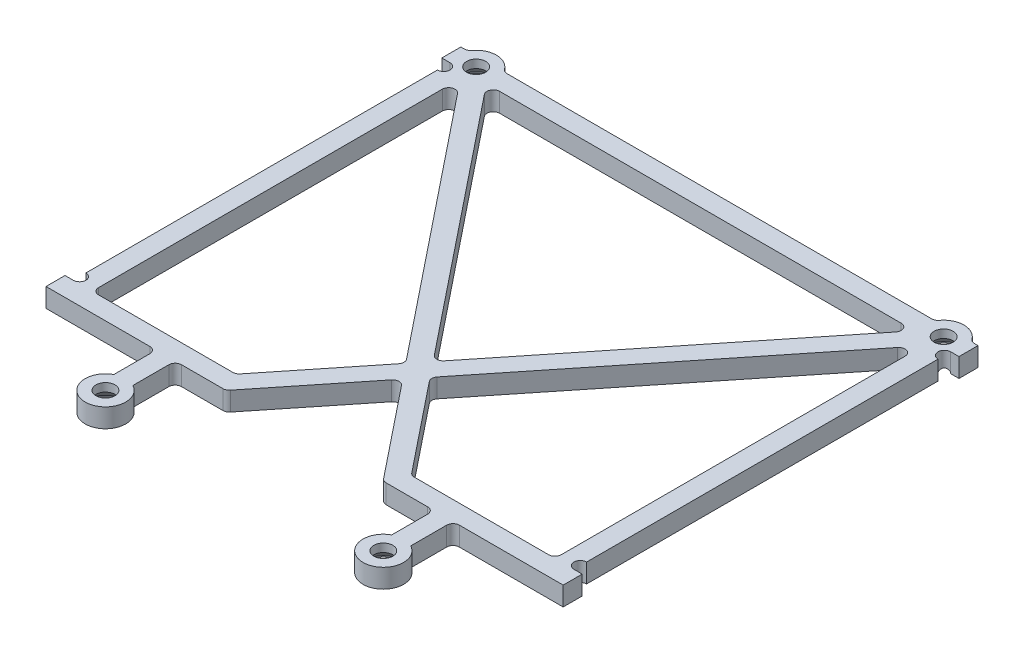
SolidWorks part; units mm, degrees
ref_plane "Front Plane" through (0, 0, 0) normal (0, 0, 1) x (1, 0, 0)
ref_plane "Top Plane" through (0, 0, 0) normal (0, 1, 0) x (1, 0, 0)
ref_plane "Right Plane" through (0, 0, 0) normal (1, 0, 0) x (0, 0, -1)
sketch "Sketch1" plane through (0, 0, 0) normal (0, 1, 0) x (1, 0, 0)
  line L0 (-36.88, 36.725) -> (36.88, 36.725) construction
  line L1 (-39.5, -24.225) -> (-39.5, 35.225)
  line L2 (21.92, -36.725) -> (-21.92, -36.725) construction
  line L3 (-36.5, -24.225) -> (-36.5, 35.225)
  line L4 (0, -40.095) -> (0, -36.725) construction
  line L5 (0, 36.725) -> (0, -36.725) construction
  line L6 (40.8, 38.225) -> (-40.8, 38.225)
  line L9 (40.8, 38.225) -> (40.8, 35.225)
  line L17 (40.8, 35.225) -> (-40.8, 35.225)
  line L18 (-40.8, 38.225) -> (-40.8, 35.225)
  line L23 (40.8, 38.225) -> (-40.8, 35.225) construction
  line L24 (40.8, 35.225) -> (-40.8, 38.225) construction
  line L60 (-21.92, -36.725) -> (36.88, 36.725) construction
  line L62 (21.92, -36.725) -> (-36.88, 36.725) construction
  line L66 (23.091, -35.7876) -> (-35.709, 37.6624)
  line L67 (20.749, -37.6624) -> (-38.051, 35.7876)
  line L68 (-20.749, -37.6624) -> (38.051, 35.7876)
  line L69 (-23.091, -35.7876) -> (35.709, 37.6624)
  line L71 (-36.5, 5.5) -> (-39.5, 5.5) construction
  line L73 (36.5, -24.225) -> (36.5, 35.225)
  line L74 (39.5, -24.225) -> (39.5, 35.225)
  line L75 (-36.5, -24.225) -> (-36.5, -27.225) construction
  line L76 (-40.8, -24.225) -> (40.8, -24.225)
  line L77 (-40.8, -24.225) -> (-40.8, -27.225)
  line L78 (-40.8, -27.225) -> (40.8, -27.225)
  line L79 (40.8, -24.225) -> (40.8, -27.225)
  line L80 (-40.8, -24.225) -> (40.8, -27.225) construction
  line L81 (-40.8, -27.225) -> (40.8, -24.225) construction
  line L82 (-21.92, -36.725) -> (-21.92, -27.225) construction
  line L84 (-23.42, -27.225) -> (-20.42, -27.225)
  line L85 (-23.42, -27.225) -> (-23.42, -33.8983)
  line L86 (-23.42, -33.8983) -> (-20.42, -33.8983)
  line L87 (-20.42, -27.225) -> (-20.42, -33.8983)
  line L88 (-23.42, -27.225) -> (-20.42, -33.8983) construction
  line L89 (-23.42, -33.8983) -> (-20.42, -27.225) construction
  line L90 (20.42, -27.225) -> (20.42, -33.8983)
  line L91 (23.42, -27.225) -> (23.42, -33.8983)
  circle A0 centre (21.92, -36.725) radius 1.5
  circle A1 centre (-21.92, -36.725) radius 1.5
  circle A2 centre (-36.88, 36.725) radius 1.5
  circle A3 centre (36.88, 36.725) radius 1.5
  circle A4 centre (-36.88, 36.725) radius 3.2
  circle A5 centre (-21.92, -36.725) radius 3.2
  circle A6 centre (21.92, -36.725) radius 3.2
  circle A7 centre (36.88, 36.725) radius 3.2
  circle A8 centre (0, -40.095) radius 16
  circle A9 centre (-39.5, 34.225) radius 1
  circle A10 centre (39.5, 34.225) radius 1
  circle A11 centre (-39.5, -23.225) radius 1
  circle A12 centre (39.5, -23.225) radius 1
  point P10 (0, 0)
  point P18 (-21.92, -30.5617)
  point P58 (0, -25.725)
  dimension "D4" = 3
  dimension "D5" = 6.4
  dimension "D6" = 32
  dimension "D9" = 3
  dimension "D17" = 2
  dimension "D1" = 74.958
  dimension "D2" = 43.84
  dimension "D3" = 73.76
  dimension "D7" = 3.37
  dimension "D8" = 81.6
  dimension "D10" = 79
  dimension "D13" = 1.5
  dimension "D14" = 1.5
  dimension "D15" = 1.5
  dimension "D16" = 1.5
  dimension "D18" = 11
extrude "Shape" add sketch "Sketch1" along normal blind 3 contours L9 | L9 | A4 L6 L18 L17 | L6 A4 | L6 A4 L17 L67 A2 | L66 A4 L6 A2 | L17 A4 L66 A2 | L67 A4 L17 L3 | L67 L3 L17 | A2 L67 L17 | A9 A4 L3 L67 L17 | A11 L76 L3 A4 A9 L1 | A4 L67 L69 L66 L17 | A4 L17 L66 | A7 L6 A4 L66 L17 L69 | L6 A7 L69 A3 | L6 A7 | L17 A7 L6 A3 L68 | A7 L17 L9 L6 | A7 A10 L17 L68 L73 | A3 L17 L68 | L69 A7 L17 A3 | L17 A7 L68 L73 | L73 L68 L17 | A7 L69 L17 | A7 L17 L69 L66 L68 | L76 A12 L74 A10 A7 L73 | L69 L67 L68 L66 | L69 L76 L68 L67 | L67 L76 L66 L68 | L77 L78 L69 L76 | A5 L69 L87 L78 L85 | A5 L87 L69 | L86 A5 L69 | L69 A5 L86 | L86 A5 L68 A1 L69 | L68 A5 L86 L69 A1 | L69 L78 L68 L76 | L67 L78 L66 L76 | L79 L76 L66 L78 | A6 L91 L78 L90 L66 | A6 L66 L90 | A6 L66 A0 L67 | L66 A6 L67 A0 region at (-27.9084, 0, 25.7017) region at (-37.9894, 0, -4.9296) region at (-37.7315, 0, -34.3772) region at (-13.114, 0, 25.725) region at (-6.4791, 0, 17.3668) region at (-21.9608, 0, 30.3398) region at (-36.8669, 0, -34.7667) region at (-35.5453, 0, -34.5717) region at (-17.9573, 0, -13.0823) region at (0, 0, 9.3436) region at (-39.0008, 0, -36.743) region at (-40.3721, 0, -36.725) region at (-22.2364, 0, 33.7343) region at (-22.4993, 0, 33.9863) region at (-35.0617, 0, -35.8515) region at (-37.5447, 0, -35.3415) region at (-33.9168, 0, -35.3014) region at (-20.7161, 0, 33.2949) region at (6.4791, 0, 17.3668) region at (17.9573, 0, -13.0823) region at (-36.88, 0, -38.9233) region at (-20.5884, 0, 35.1329) region at (-21.0809, 0, 33.7851) region at (0, 0, -36.7255) region at (-34.6096, 0, -37.2433) region at (13.114, 0, 25.725) region at (33.9168, 0, -35.3014) region at (27.9084, 0, 25.7017) region at (35.5453, 0, -34.5717) region at (35.0617, 0, -35.8515) region at (34.6096, 0, -37.2433) region at (36.88, 0, -38.9233) region at (20.6063, 0, 35.084) region at (19.7951, 0, 36.6157) region at (37.9894, 0, -4.9296) region at (36.8669, 0, -34.7667) region at (37.7315, 0, -34.3772) region at (39.0008, 0, -36.743) region at (40.3721, 0, -36.725) region at (20.7161, 0, 33.2949) region at (21.9608, 0, 30.3398) region at (37.5447, 0, -35.3415)
fillet "Mill fillets" radius 1 22 edges at (39.7067, 1.5, -38.225) (34.0533, 1.5, -38.225) (-39.7067, 1.5, -38.225) (-34.0533, 1.5, -38.225) (1.9214, 1.5, 9.3436) (-1.9214, 1.5, 9.3436) (33.7577, 1.5, -35.225) (-33.7577, 1.5, -35.225) (0, 1.5, 11.7438) (-36.5, 1.5, 24.225) (13.8346, 1.5, 24.225) (36.5, 1.5, 24.225) (-13.8346, 1.5, 24.225) (36.5, 1.5, -33.8501) (-36.5, 1.5, -33.8501) (0, 1.5, 6.9435) (-23.42, 1.5, 27.225) (20.42, 1.5, 27.225) (23.42, 1.5, 27.225) (-20.42, 1.5, 27.225) (12.3934, 1.5, 27.225) (-12.3934, 1.5, 27.225)
hole_wizard "M3 countersunks" positions "Sketch2" profile "Sketch3" countersink size "M3" standard "ANSI Metric" end condition through all
sketch "Sketch2" plane through (0, 0, 0) normal (0, -1, 0) x (-1, 0, 0)
  point P0 (21.92, -36.725)
  point P3 (-21.92, -36.725)
  point P6 (-36.88, 36.725)
  point P9 (36.88, 36.725)
sketch "Sketch3" plane through (-21.92, 0, 36.725) normal (1, 0, 0) x (0, 0, -1)
  line L0 (0, 0) -> (0, 3)
  line L1 (0, 3) -> (1.5, 3)
  line L2 (1.5, 3) -> (1.5, 1.7)
  line L3 (1.5, 1.7) -> (3, 0.2)
  line L4 (3, 0.2) -> (3, 0)
  line L6 (3, 0) -> (0, 0)
  line L7 (-1.5, 1.7) -> (-3, 0.2) construction
  line L11 (0, -6.35) -> (0, 107.95) construction
  dimension "Thru Hole Dia." = 3
  dimension "Thru Hole Depth" = 3
  dimension "C'Sink Dia." = 6
  dimension "C'Sink Angle" = 90
  dimension "Head Clearance" = 0.2
